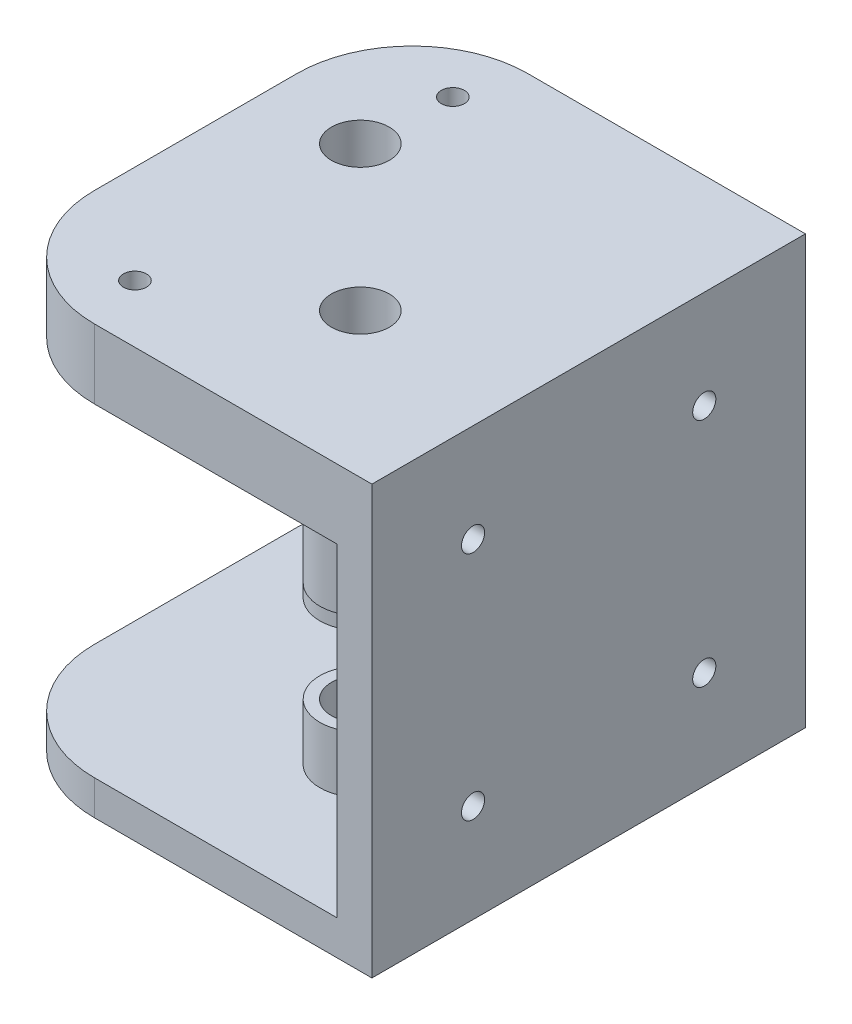
SolidWorks part; units mm, degrees
ref_plane "Front Plane" through (0, 0, 0) normal (0, 0, 1) x (1, 0, 0)
ref_plane "Top Plane" through (0, 0, 0) normal (0, 1, 0) x (1, 0, 0)
ref_plane "Right Plane" through (0, 0, 0) normal (1, 0, 0) x (0, 0, -1)
sketch "TopSketch1" plane through (0, 0, 0) normal (0, 1, 0) x (1, 0, 0)
  line L1 (0, 0) -> (34, 0)
  line L2 (0, 0) -> (0, 37.5)
  line L3 (0, 37.5) -> (34, 37.5)
  line L4 (34, 0) -> (34, 37.5)
  circle A0 centre (8.5, 32.5) radius 1
  circle A1 centre (8.5, 5) radius 1
  circle A2 centre (20.5, 12.5) radius 2.5
  circle A3 centre (8, 25) radius 2.5
  dimension "D7" = 2
  dimension "D8" = 5
  dimension "D2" = 12.5
  dimension "D3" = 12.5
  dimension "D4" = 5
  dimension "D5" = 5
  dimension "D10" = 37.5
  dimension "D9" = 12.5
  dimension "D12" = 13.5
  dimension "D6" = 25.5
  dimension "D11" = 8
  dimension "D13" = 12.5
extrude "Boss-Extrude1" add sketch "TopSketch1" along normal blind 6
sketch "TopLeftRiser" plane through (0, 0, 0) normal (0, -1, 0) x (1, 0, 0)
  line L0 (5.75, -27.681) -> (5.75, -37.5)
  line L1 (34, -37.5) -> (0, -37.5) construction
  line L2 (5.75, -37.5) -> (10.25, -37.5)
  line L3 (10.25, -37.5) -> (10.25, -27.681)
  arc A0 (10.25, -27.681) -> (5.75, -27.681) centre (8, -25) ccw
  circle A1 centre (8, -25) radius 2.5 construction
  circle A2 centre (8, -25) radius 2.5
  point P12 (8, -37.5)
  dimension "D1" = 7
  dimension "D2" = 4.5
extrude "TopLeftRiserBoss-Extrude2" add sketch "TopLeftRiser" along normal blind 4.9
sketch "TopRightRiser" plane through (0, 0, 0) normal (0, -1, 0) x (1, 0, 0)
  line L0 (18.25, -15.181) -> (18.25, -37.5)
  line L1 (34, -37.5) -> (10.25, -37.5) construction
  line L2 (18.25, -37.5) -> (22.75, -37.5)
  line L3 (22.75, -37.5) -> (22.75, -15.181)
  line L4 (5.75, -37.5) -> (10.25, -37.5) construction
  circle A0 centre (20.5, -12.5) radius 2.5
  circle A1 centre (20.5, -12.5) radius 2.5 construction
  arc A2 (22.75, -15.181) -> (18.25, -15.181) centre (20.5, -12.5) ccw
  arc A3 (10.25, -27.681) -> (5.75, -27.681) centre (8, -25) ccw construction
  point P15 (20.5, -37.5)
extrude "topRightRiserBoss-Extrude3" add sketch "TopRightRiser" along normal blind 14.4
sketch "MidWallSketch3" plane through (0, 0, 0) normal (0, -1, 0) x (1, 0, 0)
  line L1 (0, -34.5) -> (10.25, -34.5)
  line L2 (0, -34.5) -> (0, -37.5)
  line L3 (0, -37.5) -> (10.25, -37.5)
  line L4 (10.25, -34.5) -> (10.25, -37.5)
  line L5 (18.25, -34.5) -> (22.75, -34.5)
  line L6 (18.25, -34.5) -> (18.25, -37.5)
  line L7 (18.25, -37.5) -> (22.75, -37.5)
  line L8 (22.75, -34.5) -> (22.75, -37.5)
  line L9 (34, 0) -> (34, -37.5)
  line L10 (34, -37.5) -> (31, -37.5)
  line L11 (31, -37.5) -> (31, 0)
  line L14 (10.25, -37.5) -> (10.25, -27.681) construction
  line L15 (0, -37.5) -> (0, 0) construction
  line L16 (34, -37.5) -> (0, -37.5) construction
  line L17 (31, 0) -> (34, 0)
  line L19 (34, 0) -> (34, -37.5) construction
  line L20 (0, 0) -> (34, 0) construction
  line L21 (22.75, -37.5) -> (22.75, -15.181) construction
  line L22 (18.25, -15.181) -> (18.25, -37.5) construction
  dimension "D1" = 3
extrude "WallBoss-Extrude4" add sketch "MidWallSketch3" along normal blind 28
sketch "BottomSketch4" plane through (0, -28, 0) normal (0, -1, 0) x (1, 0, 0)
  line L0 (0, 0) -> (34, 0) construction
  line L1 (0, 0) -> (34, 0)
  line L2 (0, 0) -> (0, -37.5)
  line L3 (0, -37.5) -> (34, -37.5)
  line L4 (34, 0) -> (34, -37.5)
  line L5 (34, 0) -> (34, -37.5) construction
  line L6 (34, -37.5) -> (0, -37.5) construction
extrude "BottomBoss-Extrude5" add sketch "BottomSketch4" along normal blind 3
sketch "LowerLeftRiser" plane through (0, -28, 0) normal (0, 1, 0) x (1, 0, 0)
  line L0 (5.75, 27.681) -> (5.75, 34.5)
  line L1 (5.75, 34.5) -> (10.25, 34.5)
  line L2 (10.25, 34.5) -> (10.25, 27.681)
  line L3 (5.75, 34.5) -> (10.25, 34.5) construction
  line L4 (5.75, 27.681) -> (5.75, 34.5) construction
  line L5 (10.25, 34.5) -> (10.25, 27.681) construction
  circle A0 centre (8, 25) radius 2.5
  arc A1 (5.75, 27.681) -> (10.25, 27.681) centre (8, 25) ccw
  circle A2 centre (8, 25) radius 2.5 construction
  arc A3 (5.75, 27.681) -> (10.25, 27.681) centre (8, 25) ccw construction
extrude "LowerLeftRiserBoss-Extrude6" add sketch "LowerLeftRiser" along normal blind 14.4
sketch "LowerRightRiser" plane through (0, -28, 0) normal (0, 1, 0) x (1, 0, 0)
  line L0 (18.25, 15.181) -> (18.25, 34.5)
  line L1 (18.25, 34.5) -> (22.75, 34.5)
  line L2 (22.75, 34.5) -> (22.75, 15.181)
  line L3 (18.25, 34.5) -> (22.75, 34.5) construction
  line L4 (18.25, 15.181) -> (18.25, 34.5) construction
  line L5 (22.75, 34.5) -> (22.75, 15.181) construction
  circle A0 centre (20.5, 12.5) radius 2.5
  circle A1 centre (20.5, 12.5) radius 2.5 construction
  arc A2 (18.25, 15.181) -> (22.75, 15.181) centre (20.5, 12.5) ccw
  arc A3 (18.25, 15.181) -> (22.75, 15.181) centre (20.5, 12.5) ccw construction
extrude "LowerRightRiserBoss-Extrude7" add sketch "LowerRightRiser" along normal blind 4.9
fillet "Fillet1" radius 10 3 edges at (0, -29.5, 0) (0, 3, 0) (0, -12.5, -37.5)
sketch "GBMountingHolesSketch7" plane through (34, 0, 0) normal (1, 0, 0) x (0, 0, -1)
  line L0 (37.5, 6) -> (37.5, -31) construction
  line L1 (0, 6) -> (37.5, 6) construction
  line L2 (37.5, -31) -> (0, -31) construction
  line L3 (0, 6) -> (0, -31) construction
  circle A0 centre (8.75, -2.5) radius 1
  circle A1 centre (8.75, -22.5) radius 1
  circle A2 centre (28.75, -22.5) radius 1
  circle A3 centre (28.75, -2.5) radius 1
  dimension "D7" = 2
  dimension "D1" = 20
  dimension "D2" = 8.75
  dimension "D3" = 8.5
  dimension "D4" = 20
  dimension "D5" = 8.5
  dimension "D6" = 8.75
sketch "TopLeftInset" plane through (0, -4.9, 0) normal (0, -1, 0) x (1, 0, 0)
  line L0 (5.75, -27.681) -> (5.75, -34.5)
  line L1 (5.75, -34.5) -> (10.25, -34.5)
  line L2 (10.25, -34.5) -> (10.25, -27.681)
  line L3 (10.25, -34.5) -> (5.75, -34.5) construction
  line L4 (5.75, -34.5) -> (5.75, -27.681) construction
  line L5 (10.25, -27.681) -> (10.25, -34.5) construction
  arc A0 (5.75, -27.681) -> (10.25, -27.681) centre (8, -25) ccw
  arc A1 (10.25, -27.681) -> (5.75, -27.681) centre (8, -25) ccw construction
extrude "TopLeftInsetCut-Extrude1" cut sketch "TopLeftInset" against normal blind 1
sketch "TopRightInset" plane through (0, -14.4, 0) normal (0, -1, 0) x (1, 0, 0)
  line L0 (18.25, -15.181) -> (18.25, -34.5)
  line L1 (18.25, -34.5) -> (22.75, -34.5)
  line L2 (22.75, -34.5) -> (22.75, -15.181)
  line L3 (22.75, -34.5) -> (18.25, -34.5) construction
  line L4 (18.25, -34.5) -> (18.25, -15.181) construction
  line L5 (22.75, -15.181) -> (22.75, -34.5) construction
  arc A0 (18.25, -15.181) -> (22.75, -15.181) centre (20.5, -12.5) ccw
  arc A1 (22.75, -15.181) -> (18.25, -15.181) centre (20.5, -12.5) ccw construction
extrude "TopRightInsetCut-Extrude2" cut sketch "TopRightInset" against normal blind 1
sketch "LowerLeftInset" plane through (0, -13.6, 0) normal (0, 1, 0) x (1, 0, 0)
  line L0 (5.75, 27.681) -> (5.75, 34.5)
  line L1 (5.75, 34.5) -> (10.25, 34.5)
  line L2 (10.25, 34.5) -> (10.25, 27.681)
  line L3 (5.75, 34.5) -> (10.25, 34.5) construction
  line L4 (5.75, 27.681) -> (5.75, 34.5) construction
  line L5 (10.25, 34.5) -> (10.25, 27.681) construction
  arc A0 (10.25, 27.681) -> (5.75, 27.681) centre (8, 25) ccw
  arc A1 (5.75, 27.681) -> (10.25, 27.681) centre (8, 25) ccw construction
extrude "LowerLeftInsetCut-Extrude3" cut sketch "LowerLeftInset" against normal blind 1
sketch "LowerRightInset" plane through (0, -23.1, 0) normal (0, 1, 0) x (1, 0, 0)
  line L0 (18.25, 15.181) -> (18.25, 34.5)
  line L1 (18.25, 34.5) -> (22.75, 34.5)
  line L2 (22.75, 34.5) -> (22.75, 15.181)
  line L3 (18.25, 34.5) -> (22.75, 34.5) construction
  line L4 (18.25, 15.181) -> (18.25, 34.5) construction
  line L5 (22.75, 34.5) -> (22.75, 15.181) construction
  arc A2 (22.75, 15.181) -> (18.25, 15.181) centre (20.5, 12.5) ccw
  arc A3 (18.25, 15.181) -> (22.75, 15.181) centre (20.5, 12.5) ccw construction
extrude "LowerRightInsetCut-Extrude4" cut sketch "LowerRightInset" against normal blind 1
extrude "GBMountingHolesCut-Extrude5" cut sketch "GBMountingHolesSketch7" against normal blind 3
sketch "PushPinHoleSketch1" plane through (0, -31, 0) normal (0, -1, 0) x (1, 0, 0)
  circle A0 centre (20.5, -12.5) radius 1
  circle A1 centre (8, -25) radius 1
  circle A2 centre (8, -25) radius 2.5 construction
  circle A3 centre (20.5, -12.5) radius 2.5 construction
  dimension "D1" = 2
extrude "PushPinHoleCut-Extrude1" cut sketch "PushPinHoleSketch1" against normal through all
sketch "BottomLeftMountHoleAccessSketch1" plane through (5.75, 0, 0) normal (-1, 0, 0) x (0, 0, 1)
  circle A0 centre (-28.75, -22.5) radius 1
  dimension "D1" = 2
extrude "BottomLeftMountHoleAccessCut-Extrude2" cut sketch "BottomLeftMountHoleAccessSketch1" against normal blind 15 and the other way blind 10
sketch "TopLeftMountHoleAccessSketch2" plane through (18.25, 0, 0) normal (-1, 0, 0) x (0, 0, 1)
  circle A0 centre (-28.75, -2.5) radius 1
  circle A1 centre (-28.75, -22.5) radius 1 construction
extrude "TopLeftMountHoleAccessCut-Extrude3" cut sketch "TopLeftMountHoleAccessSketch2" against normal blind 5 and the other way through all
equation "\"GABDepth\"= \"GABDistanceFromBackToFirstPulley\" + \"GABPulleyDDistanceBetween\" + \"GABDistanceFromPulleyToFront\""
equation "\"GABWidth\"= \"StandardWallThickness\" + \"GABDistanceFromLSideToPulley\" + \"GABPulleyWDistanceBetween\" + \"GABDistanceFromPulleyToRSide\""
equation "\"GABLowerHeight\"= 3mm"
equation "\"GABUpperHeight\"= 6mm"
equation "\"GABMidWallHeight\"= 28mm'Must equal 28 or changes alignment"
equation "\"StandardWallThickness\"= 3mm"
equation "\"GABMidShortRiserHeight\"= \"GABMidWallHeight\" / 2 - \"20TGT2PulleyWidth\"'Equals 5.3"
equation "\"LinearGBMountHolesXDistance\"= 20mm'Spec"
equation "\"GABHeight\"= \"GABLowerHeight\" + \"GABMidWallHeight\" + \"GABUpperHeight\""
equation "\"GBMountingHoleDiameter\"= 2mm"
equation "\"GABMidLongRiserHeight\"= \"GABMidWallHeight\" - \"GABMidShortRiserHeight\" - \"20TGT2PulleyWidth\"'Equals 14"
equation "\"GABLRClampHoleOffsetFromSide\"= 5mm"
equation "\"GABDistanceFromBackToFirstPulley\"= 13.5mm"
equation "\"GABPulleyDDistanceBetween\"= 12.5mm'From the100"
equation "\"GABPulleyWDistanceBetween\"= 14.5mm'From the100"
equation "\"GABDistanceFromPulleyToFront\"= 8mm"
equation "\"GABDistanceFromLSideToPulley\"= 9.5mm + \"StandardWallThickness\""
equation "\"GABDistanceFromPulleyToRSide\"= 7.5mm"
equation "\"GABDistanceToFrontClampHoles\"= 8.5mm"
equation "\"SteelShaft5mmHoleDiameter\"= 5mm"
equation "\"20TGT2PulleyWidth\"= 8.7mm'The STL of the Pulley in the diagram is a bit larger"
equation "\"7mmx1mmSpacerDiameter\"= 7mm"
equation "\"7mmx1mmSpacerHeight\"= 1mm"
equation "\"GABRiserBossOffset\"= 0.8mm'Aligns Pulleys"
equation "\"D2@TopSketch1\" = \"GABPulleyDDistanceBetween\""
equation "\"D3@TopSketch1\" = \"GABPulleyDDistanceBetween\""
equation "\"D4@TopSketch1\" = \"GABLRClampHoleOffsetFromSide\""
equation "\"D5@TopSketch1\" = \"GABLRClampHoleOffsetFromSide\""
equation "\"D8@TopSketch1\" = \"SteelShaft5mmHoleDiameter\""
equation "\"D10@TopSketch1\" = \"GABWidth\""
equation "\"D9@TopSketch1\" = \"GABDistanceFromLSideToPulley\""
equation "\"D12@TopSketch1\"=\"GABDistanceFromBackToFirstPulley\""
equation "\"D1@Boss-Extrude1\"=\"GABUpperHeight\""
equation "\"D1@TopLeftRiser\" = \"7mmx1mmSpacerDiameter\""
equation "\"D1@TopLeftRiserBoss-Extrude2\"=\"GABMidShortRiserHeight\" - \"GABRiserBossOffset\" / 2"
equation "\"D1@topRightRiserBoss-Extrude3\"=\"GABMidLongRiserHeight\" + \"GABRiserBossOffset\"/2"
equation "\"D1@WallBoss-Extrude4\" = \"GABMidWallHeight\""
equation "\"D1@BottomBoss-Extrude5\" = \"GABLowerHeight\""
equation "\"D1@LowerLeftRiserBoss-Extrude6\"=\"GABMidLongRiserHeight\" + \"GABRiserBossOffset\"/2"
equation "\"D1@LowerRightRiserBoss-Extrude7\"=\"GABMidShortRiserHeight\"-\"GABRiserBossOffset\"/2"
equation "\"D1@GBMountingHolesSketch7\" = \"LinearGBMountHolesXDistance\""
equation "\"D2@GBMountingHolesSketch7\" =  ( \"GABWidth\" - \"LinearGBMountHolesXDistance\" )  / 2"
equation "\"D3@GBMountingHolesSketch7\" =  ( \"GABHeight\" - \"LinearGBMountHolesXDistance\" )  / 2"
equation "\"D4@GBMountingHolesSketch7\"=\"LinearGBMountHolesYDistance\""
equation "\"D7@GBMountingHolesSketch7\"=\"GBMountingHoleDiameter\""
equation "\"D1@TopLeftInsetCut-Extrude1\" = \"7mmx1mmSpacerHeight\""
equation "\"D1@TopRightInsetCut-Extrude2\" = \"7mmx1mmSpacerHeight\""
equation "\"D1@LowerLeftInsetCut-Extrude3\" = \"7mmx1mmSpacerHeight\""
equation "\"D1@LowerRightInsetCut-Extrude4\" = \"7mmx1mmSpacerHeight\""
equation "\"D1@GBMountingHolesCut-Extrude5\" = \"StandardWallThickness\""
equation "\"D6@TopSketch1\"=\"GABDepth\" - \"GABDistanceToFrontClampHoles\""
equation "\"D11@TopSketch1\"=\"GABDistanceFromPulleyToFront\""
equation "\"LinearGBMountHolesYDistance\"= 20mm'Spec"
equation "\"StealPinPushHoleDiameter\"= 2mm"
equation "\"D1@PushPinHoleSketch1\" = \"StealPinPushHoleDiameter\""
